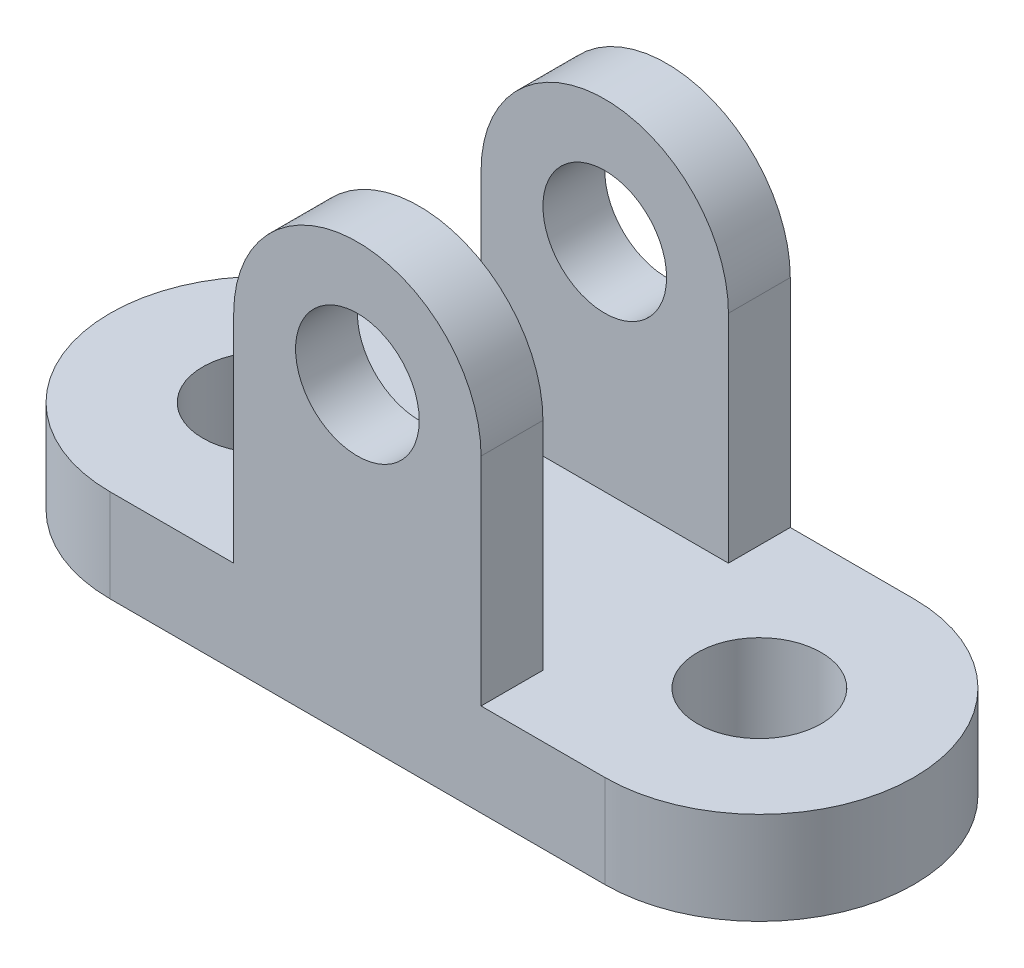
SolidWorks part; units mm, degrees
ref_plane "Front Plane" through (0, 0, 0) normal (0, 0, 1) x (1, 0, 0)
ref_plane "Top Plane" through (0, 0, 0) normal (0, 1, 0) x (1, 0, 0)
ref_plane "Right Plane" through (0, 0, 0) normal (1, 0, 0) x (0, 0, -1)
sketch "Sketch1" plane through (0, 0, 0) normal (0, 1, 0) x (1, 0, 0)
  line L0 (-40, 0) -> (40, 0) construction
  line L1 (-40, 25) -> (40, 25)
  line L2 (-40, -25) -> (40, -25)
  arc A0 (-40, 25) -> (-40, -25) centre (-40, 0) ccw
  arc A1 (40, -25) -> (40, 25) centre (40, 0) ccw
  point P3 (0, 0)
  dimension "D1" = 25
  dimension "D2" = 80
  dimension "D3" = 40
extrude "Boss-Extrude1" add sketch "Sketch1" along normal blind 15
sketch "Sketch2" plane through (0, 0, 0) normal (0, 0, 1) x (1, 0, 0)
  line L6 (-40, 15) -> (40, 15) construction
  line L7 (-20, 70) -> (20, 70)
  line L8 (-20, 70) -> (-20, 15)
  line L9 (-20, 15) -> (20, 15)
  line L10 (20, 70) -> (20, 15)
  dimension "D1" = 40
  dimension "D2" = 20
  dimension "D3" = 55
extrude "Boss-Extrude2" add sketch "Sketch2" along normal mid plane 50
fillet "Fillet1" 2 edges at (20, 70, 0) (-20, 70, 0) type full round first side face at (20, 42.5, 0) second side face at (-20, 42.5, 0) middle face at (0, 70, 0)
sketch "Sketch3" plane through (0, 15, 0) normal (0, 1, 0) x (1, 0, 0)
  line L0 (-20, 25) -> (-40, 25) construction
  line L1 (-80.5532, 15) -> (84.0732, 15)
  line L2 (-80.5532, 15) -> (-80.5532, -15)
  line L3 (-80.5532, -15) -> (84.0732, -15)
  line L4 (84.0732, 15) -> (84.0732, -15)
  line L5 (-40, -25) -> (-20, -25) construction
  dimension "D1" = 10
  dimension "D2" = 10
extrude "Cut-Extrude1" cut sketch "Sketch3" along normal through all
hole_wizard "Ø1.0mm Dowel Hole1" positions "Sketch7" profile "Sketch5" hole size "Ø1.0" standard "ISO" end condition through all
sketch "Sketch7" plane through (0, 15, 0) normal (0, 1, 0) x (1, 0, 0)
  point P0 (-40, 0)
  point P3 (40, 0)
sketch "Sketch5" plane through (-40, 15, 0) normal (1, 0, 0) x (0, 0, 1)
  line L0 (0, 0) -> (0, 15)
  line L1 (0, 15) -> (10, 15)
  line L2 (10, 15) -> (10, 0)
  line L5 (10, 0) -> (0, 0)
  line L11 (0, -6.35) -> (0, 107.95) construction
  dimension "Thru Hole Dia." = 20
  dimension "Thru Hole Depth" = 15
hole_wizard "Ø1.0mm Dowel Hole2" positions "Sketch8" profile "Sketch9" hole size "Ø1.0" standard "ISO" end condition through all
sketch "Sketch8" plane through (0, 0, 25) normal (0, 0, 1) x (1, 0, 0)
  point P0 (0, 50)
sketch "Sketch9" plane through (0, 50, 25) normal (1, 0, 0) x (0, -1, 0)
  line L0 (0, 0) -> (0, 50)
  line L1 (0, 50) -> (10, 50)
  line L2 (10, 50) -> (10, 0)
  line L5 (10, 0) -> (0, 0)
  line L11 (0, -6.35) -> (0, 107.95) construction
  dimension "Thru Hole Dia." = 20
  dimension "Thru Hole Depth" = 50
